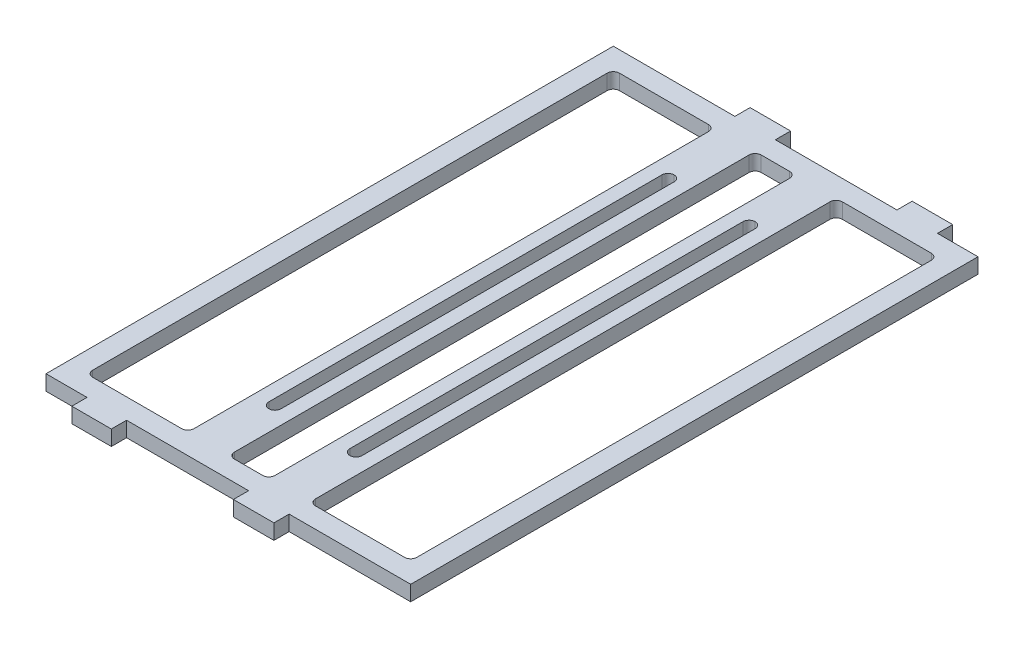
SolidWorks part; units mm, degrees
material "6061-T6 (SS)"
ref_plane "Front Plane" through (0, 0, 0) normal (0, 0, 1) x (1, 0, 0)
ref_plane "Top Plane" through (0, 0, 0) normal (0, 1, 0) x (1, 0, 0)
ref_plane "Right Plane" through (0, 0, 0) normal (1, 0, 0) x (0, 0, -1)
sketch "Sketch1" plane through (0, 0, 0) normal (0, 1, 0) x (1, 0, 0)
  line L0 (50.8, 82.55) -> (-50.8, 82.55)
  line L1 (57.15, 88.9) -> (-57.15, 88.9)
  line L2 (57.15, 88.9) -> (57.15, -88.9)
  line L3 (57.15, -88.9) -> (-57.15, -88.9)
  line L4 (-57.15, 88.9) -> (-57.15, -88.9)
  line L5 (57.15, 88.9) -> (-57.15, -88.9) construction
  line L6 (57.15, -88.9) -> (-57.15, 88.9) construction
  line L7 (-50.8, 82.55) -> (-50.8, -82.55)
  line L8 (50.8, -82.55) -> (-50.8, -82.55)
  line L9 (50.8, 82.55) -> (50.8, -82.55)
  point P0 (0, 0)
  dimension "D1" = 114.3
  dimension "D2" = 177.8
  dimension "D3" = 6.35
extrude "Boss-Extrude1" add sketch "Sketch1" along normal blind 4.7625
sketch "Sketch2" plane through (0, 0, 88.9) normal (0, 0, 1) x (1, 0, 0)
  line L0 (-57.15, 2.3813) -> (57.15, 2.3813) construction
  line L1 (-57.15, 4.7625) -> (-57.15, 0) construction
  line L2 (57.15, 4.7625) -> (57.15, 0) construction
  line L3 (-57.15, 0) -> (57.15, 0) construction
  line L4 (-31.9066, 4.7625) -> (-44.2934, 4.7625)
  line L5 (-31.9066, 4.7625) -> (-31.9066, 0)
  line L6 (-31.9066, 0) -> (-44.2934, 0)
  line L7 (-44.2934, 4.7625) -> (-44.2934, 0)
  line L8 (-31.9066, 4.7625) -> (-44.2934, 0) construction
  line L9 (-31.9066, 0) -> (-44.2934, 4.7625) construction
  line L11 (19.05, 4.7625) -> (6.35, 4.7625)
  line L12 (19.05, 4.7625) -> (19.05, 0)
  line L13 (19.05, 0) -> (6.35, 0)
  line L14 (6.35, 4.7625) -> (6.35, 0)
  line L15 (19.05, 4.7625) -> (6.35, 0) construction
  line L16 (19.05, 0) -> (6.35, 4.7625) construction
  point P6 (-38.1, 2.3813)
  point P13 (12.7, 2.3813)
  dimension "D1" = 19.05
  dimension "D2" = 50.8
  dimension "D3" = 12.7
extrude "Boss-Extrude2" add sketch "Sketch2" along normal blind 4.7625
sketch "Sketch3" plane through (0, 0, -88.9) normal (0, 0, -1) x (-1, 0, 0)
  line L0 (-57.15, 2.3813) -> (57.15, 2.3813) construction
  line L1 (-57.15, 4.7625) -> (-57.15, 0) construction
  line L2 (57.15, 4.7625) -> (57.15, 0) construction
  line L3 (-57.15, 0) -> (57.15, 0) construction
  line L4 (-31.75, 4.7625) -> (-44.45, 4.7625)
  line L5 (-31.75, 4.7625) -> (-31.75, 0)
  line L6 (-31.75, 0) -> (-44.45, 0)
  line L7 (-44.45, 4.7625) -> (-44.45, 0)
  line L8 (-31.75, 4.7625) -> (-44.45, 0) construction
  line L9 (-31.75, 0) -> (-44.45, 4.7625) construction
  line L11 (19.05, 4.7625) -> (6.35, 4.7625)
  line L12 (19.05, 4.7625) -> (19.05, 0)
  line L13 (19.05, 0) -> (6.35, 0)
  line L14 (6.35, 4.7625) -> (6.35, 0)
  line L15 (19.05, 4.7625) -> (6.35, 0) construction
  line L16 (19.05, 0) -> (6.35, 4.7625) construction
  point P6 (-38.1, 2.3812)
  point P13 (12.7, 2.3812)
  dimension "D1" = 12.7
  dimension "D2" = 12.7
  dimension "D3" = 19.05
  dimension "D4" = 50.8
extrude "Boss-Extrude3" add sketch "Sketch3" along normal blind 4.7625
sketch "Sketch4" plane through (0, 4.7625, 0) normal (0, 1, 0) x (-1, 0, 0)
  line L0 (57.15, 0) -> (-57.15, 0) construction
  line L1 (57.15, -88.9) -> (57.15, 88.9) construction
  line L2 (-57.15, 88.9) -> (-57.15, -88.9) construction
  line L3 (57.15, 88.9) -> (44.2934, 88.9) construction
  line L4 (6.35, -88.9) -> (19.05, -88.9)
  line L5 (6.35, -88.9) -> (6.35, 88.9)
  line L6 (6.35, 88.9) -> (19.05, 88.9)
  line L7 (19.05, -88.9) -> (19.05, 88.9)
  line L8 (6.35, -88.9) -> (19.05, 88.9) construction
  line L9 (6.35, 88.9) -> (19.05, -88.9) construction
  line L10 (-19.05, 88.9) -> (-57.15, 88.9) construction
  line L11 (-19.05, -88.9) -> (-6.35, -88.9)
  line L12 (-19.05, -88.9) -> (-19.05, 88.9)
  line L13 (-19.05, 88.9) -> (-6.35, 88.9)
  line L14 (-6.35, -88.9) -> (-6.35, 88.9)
  line L15 (-19.05, -88.9) -> (-6.35, 88.9) construction
  line L16 (-19.05, 88.9) -> (-6.35, -88.9) construction
  line L18 (10.795, -63.5) -> (14.605, -63.5)
  line L19 (10.795, -63.5) -> (10.795, 63.5)
  line L20 (10.795, 63.5) -> (14.605, 63.5)
  line L21 (14.605, -63.5) -> (14.605, 63.5)
  line L22 (10.795, -63.5) -> (14.605, 63.5) construction
  line L23 (10.795, 63.5) -> (14.605, -63.5) construction
  line L24 (-14.605, -63.5) -> (-10.795, -63.5)
  line L25 (-14.605, -63.5) -> (-14.605, 63.5)
  line L26 (-14.605, 63.5) -> (-10.795, 63.5)
  line L27 (-10.795, -63.5) -> (-10.795, 63.5)
  line L28 (-14.605, -63.5) -> (-10.795, 63.5) construction
  line L29 (-14.605, 63.5) -> (-10.795, -63.5) construction
  point P6 (12.7, 0)
  point P13 (-12.7, 0)
  point P20 (12.7, 0)
  point P26 (-12.7, 0)
  dimension "D1" = 12.7
  dimension "D2" = 12.7
  dimension "D3" = 12.7
  dimension "D4" = 12.7
  dimension "D5" = 127
  dimension "D6" = 3.81
  dimension "D7" = 127
  dimension "D8" = 3.81
extrude "Boss-Extrude4" add sketch "Sketch4" against normal blind 4.7625
fillet "Fillet1" radius 1.905 20 edges at (-10.795, 2.3813, -63.5) (-14.605, 2.3813, -63.5) (10.795, 2.3813, -63.5) (14.605, 2.3813, -63.5) (-10.795, 2.3813, 63.5) (-14.605, 2.3813, 63.5) (10.795, 2.3813, 63.5) (14.605, 2.3813, 63.5) (-6.35, 2.3813, 82.55) (6.35, 2.3813, 82.55) (-6.35, 2.3813, -82.55) (6.35, 2.3813, -82.55) (-19.05, 2.3813, -82.55) (-50.8, 2.3813, -82.55) (-50.8, 2.3813, 82.55) (-19.05, 2.3813, 82.55) (19.05, 2.3813, 82.55) (50.8, 2.3813, 82.55) (19.05, 2.3813, -82.55) (50.8, 2.3813, -82.55)
